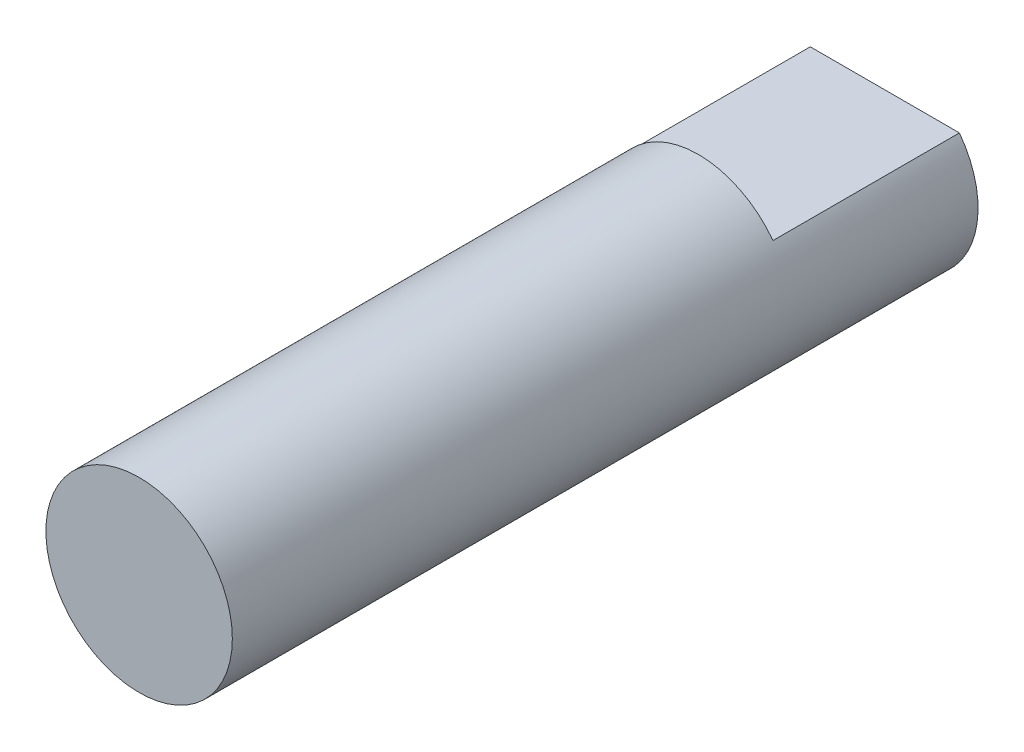
SolidWorks part; units mm, degrees
ref_plane "정면" through (0, 0, 0) normal (0, 0, 1) x (1, 0, 0)
ref_plane "윗면" through (0, 0, 0) normal (0, 1, 0) x (1, 0, 0)
ref_plane "우측면" through (0, 0, 0) normal (1, 0, 0) x (0, 0, -1)
sketch "스케치1" plane through (0, 0, 0) normal (0, 0, 1) x (1, 0, 0)
  circle A0 centre (0, 0) radius 5
  dimension "D1" = 10
extrude "보스-돌출1" add sketch "스케치1" along normal blind 40
sketch "스케치2" plane through (0, 0, 0) normal (0, 0, 1) x (1, 0, 0)
  line L0 (-4, 3) -> (4, 3)
  circle A0 centre (0, 0) radius 5 construction
  arc A1 (-4, 3) -> (4, 3) centre (0, 0) cw
  point P6 (-3.8169, 3.3141)
  point P8 (3.6735, 3.392)
  point P9 (0, 0)
  point P10 (0, 0)
  dimension "D1" = 3
extrude "컷-돌출1" cut sketch "스케치2" along normal blind 10
